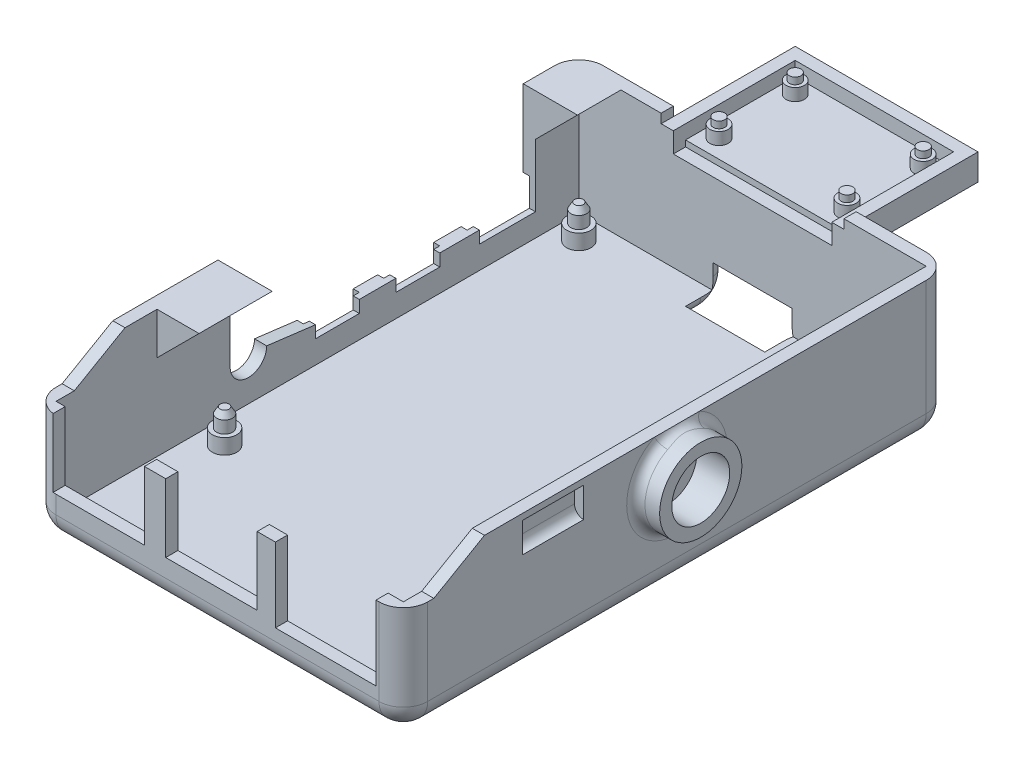
SolidWorks part; units mm, degrees
ref_plane "Płaszczyzna przednia" through (0, 0, 0) normal (0, 0, 1) x (1, 0, 0)
ref_plane "Płaszczyzna górna" through (0, 0, 0) normal (0, 1, 0) x (1, 0, 0)
ref_plane "Płaszczyzna prawa" through (0, 0, 0) normal (1, 0, 0) x (0, 0, -1)
sketch "Szkic1" plane through (0, 0, 0) normal (0, 1, 0) x (1, 0, 0)
  line L1 (-30.5, 44.9) -> (30.5, 44.9)
  line L2 (-30.5, 44.9) -> (-30.5, -44.9)
  line L3 (-30.5, -44.9) -> (30.5, -44.9)
  line L4 (30.5, 44.9) -> (30.5, -44.9)
  line L5 (-30.5, 44.9) -> (30.5, -44.9) construction
  line L6 (-30.5, -44.9) -> (30.5, 44.9) construction
  point P0 (0, 0)
  dimension "D1" = 61
  dimension "D2" = 89.8
extrude "Dodanie-wyciągnięcie1" add sketch "Szkic1" along normal blind 2
sketch "Szkic2" plane through (0, 2, 0) normal (0, 1, 0) x (1, 0, 0)
  line L0 (28.5, -42.9) -> (28.5, 42.9)
  line L1 (28.5, 42.9) -> (-28.5, 42.9)
  line L2 (-28.5, 42.9) -> (-28.5, -42.9)
  line L3 (-28.5, -42.9) -> (28.5, -42.9)
  line L4 (30.5, -44.9) -> (30.5, 44.9)
  line L5 (30.5, 44.9) -> (-30.5, 44.9)
  line L6 (-30.5, 44.9) -> (-30.5, -44.9)
  line L7 (-30.5, -44.9) -> (30.5, -44.9)
  line L8 (30.5, -44.9) -> (30.5, 44.9)
  line L9 (30.5, 44.9) -> (-30.5, 44.9)
  line L10 (-30.5, 44.9) -> (-30.5, -44.9)
  line L11 (-30.5, -44.9) -> (30.5, -44.9)
  dimension "D1" = 0
  dimension "D2" = 2
extrude "Dodanie-wyciągnięcie2" add sketch "Szkic2" along normal blind 16.15
sketch "Szkic3" plane through (0, 0, 44.9) normal (0, 0, 1) x (1, 0, 0)
  line L0 (-30.5, 18.15) -> (30.5, 18.15) construction
  line L1 (-27, 18.15) -> (-12, 18.15)
  line L2 (-27, 18.15) -> (-27, 6.95)
  line L3 (-27, 6.95) -> (-12, 6.95)
  line L4 (-12, 18.15) -> (-12, 6.95)
  line L5 (-30.5, 18.15) -> (-30.5, 0) construction
  line L6 (-8.5, 18.15) -> (6.5, 18.15)
  line L7 (-8.5, 18.15) -> (-8.5, 6.95)
  line L8 (-8.5, 6.95) -> (6.5, 6.95)
  line L9 (6.5, 18.15) -> (6.5, 6.95)
  line L10 (26, 18.15) -> (9.5, 18.15)
  line L11 (26, 18.15) -> (26, 5.95)
  line L12 (26, 5.95) -> (9.5, 5.95)
  line L13 (9.5, 18.15) -> (9.5, 5.95)
  dimension "D1" = 3.5
  dimension "D2" = 15
  dimension "D3" = 3.5
  dimension "D4" = 16.5
  dimension "D5" = 3
  dimension "D6" = 11.2
  dimension "D7" = 12.2
extrude "Wytnij-wyciągnięcie1" cut sketch "Szkic3" against normal up to surface (2 mm away) up to face at (0, 10.075, 42.9)
sketch "Szkic4" plane through (0, 0, -44.9) normal (0, 0, -1) x (-1, 0, 0)
  line L0 (-30.5, 0) -> (30.5, 0) construction
  line L1 (-6.5, 0) -> (6.5, 0)
  line L2 (-6.5, 0) -> (-6.5, 5.95)
  line L3 (-6.5, 5.95) -> (6.5, 5.95)
  line L4 (6.5, 0) -> (6.5, 5.95)
  line L5 (-6.5, 5.95) -> (-30.5, 5.95)
  line L7 (-30.5, 18.15) -> (-30.5, 0) construction
  line L8 (6.5, 5.95) -> (30.5, 5.95)
  line L9 (30.5, 18.15) -> (30.5, 0) construction
  dimension "D1" = 13
  dimension "D2" = 5.95
extrude "Wytnij-wyciągnięcie2" cut sketch "Szkic4" against normal blind 6.5 contours L2 L1 L4 L3
sketch "Szkic6" plane through (-30.5, 0, 0) normal (-1, 0, 0) x (0, 0, 1)
  line L0 (-35.77, 18.15) -> (14.33, 18.15)
  line L1 (-35.77, 18.15) -> (-35.77, 5.75)
  line L2 (-35.77, 5.75) -> (14.33, 5.75)
  line L3 (14.33, 18.15) -> (14.33, 5.75)
  line L4 (-26.57, 5.75) -> (-26.57, 7.75)
  line L5 (-26.57, 7.75) -> (-20.07, 7.75)
  line L6 (-20.07, 7.75) -> (-20.07, 5.75)
  line L7 (-12.87, 5.75) -> (-12.87, 7.75)
  line L8 (-12.87, 7.75) -> (-6.87, 7.75)
  line L9 (-6.87, 7.75) -> (-6.87, 5.75)
  line L10 (0.33, 5.75) -> (0.33, 7.75)
  line L11 (0.33, 7.75) -> (8.33, 8.75)
  line L12 (8.33, 8.75) -> (8.33, 5.75)
  line L13 (-6.87, 7.75) -> (0.33, 7.75) construction
  line L14 (-12.87, 7.75) -> (-20.07, 7.75) construction
  line L15 (-44.9, 18.15) -> (44.9, 18.15) construction
  line L16 (-44.9, 0) -> (44.9, 0) construction
  line L17 (-44.9, 18.15) -> (-44.9, 0) construction
  circle A0 centre (11.33, 8.75) radius 3
  line M7 (44.9, 18.15) -> (-44.9, 18.15)
  dimension "D2" = 6
  dimension "D1" = 50.1
  dimension "D3" = 9.2
  dimension "D4" = 7.2
  dimension "D5" = 6.5
  dimension "D6" = 6
  dimension "D7" = 2
  dimension "D8" = 5.75
  dimension "D9" = 9.13
extrude "Wytnij-wyciągnięcie4" cut sketch "Szkic6" against normal up to surface (2 mm away) contours A0 L3 L1 L2 L4 L5 L6 L7 L8 L9 L10 L11 M7 | A0 region at (-30.5, 12.5758, -12.3031) region at (-30.5, 8.75, 11.33) up to face at (-28.5, 10.075, 0)
sketch "Szkic7" plane through (0, 2, 0) normal (0, 1, 0) x (1, 0, 0)
  line L0 (24.57, 38.97) -> (24.57, -19.17) construction
  line L1 (24.57, -19.17) -> (-24.57, -19.17) construction
  line L2 (-24.57, -19.17) -> (-24.57, 38.97) construction
  line L3 (-24.57, 38.97) -> (24.57, 38.97) construction
  line L4 (0, 38.97) -> (0, -19.17) construction
  line L5 (-24.57, 9.9) -> (24.57, 9.9) construction
  line L7 (28.5, -42.9) -> (28.5, 42.9) construction
  line L8 (28.5, 42.9) -> (6.5, 42.9) construction
  line L9 (-28.5, 42.9) -> (-28.5, -42.9) construction
  line L10 (-28.5, -42.9) -> (28.5, -42.9) construction
  circle A0 centre (24.57, -19.17) radius 2
  circle A1 centre (-24.57, -19.17) radius 2
  circle A2 centre (24.57, 38.97) radius 2
  circle A3 centre (-24.57, 38.97) radius 2
  point P12 (0, 9.9)
  dimension "D1" = 4
  dimension "D2" = 3.93
  dimension "D5" = 23.73
  dimension "D3" = 3.93
  dimension "D4" = 3.93
extrude "Dodanie-wyciągnięcie3" add sketch "Szkic7" along normal blind 2.5
ref_plane "haczyki-przednia" through (0, 0, -9.9) normal (0, 0, 1) x (1, 0, 0)
ref_plane "haczyki-prawa" through (0, 0, 0) normal (-1, 0, 0) x (0, 0, 1)
sketch "Szkic8" plane through (0, 4.5, 0) normal (0, 1, 0) x (1, 0, 0)
  circle A0 centre (-24.57, 38.97) radius 1.3
  dimension "D1" = 2.6
extrude "Dodanie-wyciągnięcie4" add sketch "Szkic8" along normal blind 2
sketch "Szkic9" plane through (0, 6.5, 0) normal (0, 1, 0) x (1, 0, 0)
  circle A1 centre (-24.57, 38.97) radius 1.3
  circle A2 centre (-24.57, 38.97) radius 1.3
  dimension "D1" = 0
extrude "Dodanie-wyciągnięcie5" add sketch "Szkic9" along normal blind 1 draft 30
mirror "Lustro1" about plane through (0, 0, 0) normal (-1, 0, 0) of "Dodanie-wyciągnięcie5", "Dodanie-wyciągnięcie4"
mirror "Lustro2" about plane through (0, 0, -9.9) normal (0, 0, 1) of "Lustro1"
sketch "Szkic11" plane through (0, 18.15, 0) normal (0, 1, 0) x (1, 0, 0)
  line L0 (-28.5, 35.77) -> (-30.5, 35.77)
  line L1 (-30.5, 35.77) -> (-30.5, 44.9)
  line L2 (-30.5, 44.9) -> (-20.5, 44.9)
  line L3 (30.5, 44.9) -> (-30.5, 44.9) construction
  line L4 (-20.5, 44.9) -> (-20.5, 42.9)
  line L5 (28.5, 42.9) -> (-28.5, 42.9) construction
  line L6 (-20.5, 42.9) -> (-28.5, 42.9)
  line L7 (-28.5, 42.9) -> (-28.5, 35.77)
  line L8 (-30.5, -14.33) -> (-28.5, -14.33)
  line L9 (-28.5, -14.33) -> (-28.5, -44.9)
  line L10 (-30.5, -44.9) -> (-27, -44.9) construction
  line L11 (-28.5, -44.9) -> (-30.5, -44.9)
  line L12 (-30.5, -44.9) -> (-30.5, -14.33)
  dimension "D1" = 10
extrude "Dodanie-wyciągnięcie6" add sketch "Szkic11" along normal blind 4.8
sketch "Szkic12" plane through (-30.5, 0, 0) normal (-1, 0, 0) x (0, 0, 1)
  line L5 (44.9, 18.15) -> (39.9, 18.15)
  line L6 (44.9, 22.95) -> (44.9, 0) construction
  line L7 (39.9, 18.15) -> (31.5862, 22.95)
  line L8 (14.33, 22.95) -> (44.9, 22.95) construction
  line L9 (31.5862, 22.95) -> (44.9, 22.95)
  line L10 (44.9, 22.95) -> (44.9, 18.15)
  line L11 (44.9, 18.15) -> (42.9, 18.15) construction
  dimension "D1" = 30
  dimension "D2" = 5
extrude "Wytnij-wyciągnięcie5" cut sketch "Szkic12" against normal up to surface (2 mm away) up to face at (-28.5, 10.469, -3.6595)
sketch "Szkic13" plane through (0, 0, 14.33) normal (0, 0, -1) x (-1, 0, 0)
  line L0 (28.5, 22.95) -> (21.6, 22.95)
  line L1 (21.6, 22.95) -> (28.5, 16.05)
  line L2 (28.5, 22.95) -> (28.5, 8.75) construction
  line L3 (28.5, 16.05) -> (28.5, 22.95)
  dimension "D1" = 45
  dimension "D2" = 6.9
extrude "Dodanie-wyciągnięcie7" add sketch "Szkic13" against normal blind 12
sketch "Szkic14" plane through (0, 0, -35.77) normal (0, 0, 1) x (1, 0, 0)
  line L0 (-21.6, 22.95) -> (-28.5, 22.95)
  line L1 (-28.5, 22.95) -> (-28.5, 16.05)
  line L5 (-21.6, 22.95) -> (-30.5, 22.95)
  line L6 (-28.5, 16.05) -> (-21.6, 22.95)
  line L7 (-28.5, 8.75) -> (-28.5, 16.05)
  line L8 (-30.5, 8.75) -> (-28.5, 8.75)
  line L9 (-30.5, 22.95) -> (-30.5, 8.75)
  line L11 (-28.5, 16.05) -> (-21.6, 22.95)
  dimension "D1" = 0
extrude "Dodanie-wyciągnięcie8" add sketch "Szkic14" against normal up to surface (7.13 mm away) up to face at (-4.1, 10.21, -42.9)
sketch "Szkic15" plane through (-30.5, 0, 0) normal (-1, 0, 0) x (0, 0, 1)
  line L0 (14.33, 22.95) -> (31.5862, 22.95) construction
  line L1 (-39.9, 21.95) -> (-36.77, 21.95)
  line L2 (-39.9, 21.95) -> (-39.9, 17.05)
  line L3 (-39.9, 17.05) -> (-36.77, 17.05)
  line L4 (-36.77, 21.95) -> (-36.77, 17.05)
  line L5 (15.33, 21.95) -> (25.33, 21.95)
  line L6 (15.33, 21.95) -> (15.33, 17.05)
  line L7 (15.33, 17.05) -> (25.33, 17.05)
  line L8 (25.33, 21.95) -> (25.33, 17.05)
  line L9 (-44.9, 22.95) -> (-44.9, 0) construction
  line L10 (14.33, 22.95) -> (14.33, 8.75) construction
  line L11 (26.33, 16.05) -> (14.33, 16.05) construction
  line L12 (26.33, 16.05) -> (26.33, 22.95) construction
  line L15 (-35.77, 22.95) -> (-35.77, 5.75) construction
  dimension "D1" = 1
  dimension "D2" = 1
  dimension "D3" = 1
  dimension "D4" = 1
  dimension "D5" = 1
  dimension "D6" = 5
extrude "Wytnij-wyciągnięcie6" cut sketch "Szkic15" against normal up to surface (7.9 mm away) up to face at (-25.05, 19.5, -39.335)
sketch "Szkic16" plane through (0, 0, -39.9) normal (0, 0, 1) x (1, 0, 0)
  line L0 (-27.5, 17.05) -> (-22.6, 21.95)
  line L1 (-22.6, 21.95) -> (-24.0142, 21.95)
  line L2 (-22.6, 21.95) -> (-30.5, 21.95) construction
  line L3 (-24.0142, 21.95) -> (-28.9142, 17.05)
  line L4 (-27.5, 17.05) -> (-30.5, 17.05) construction
  line L5 (-28.9142, 17.05) -> (-27.5, 17.05)
  dimension "D1" = 1
extrude "Dodanie-wyciągnięcie9" add sketch "Szkic16" along normal up to surface (3.13 mm away) up to face at (-27.775, 19.5, -36.77)
sketch "Szkic17" plane through (0, 0, 25.33) normal (0, 0, -1) x (-1, 0, 0)
  line L0 (27.5, 17.05) -> (28.9142, 17.05)
  line L1 (27.5, 17.05) -> (30.5, 17.05) construction
  line L2 (28.9142, 17.05) -> (24.0142, 21.95)
  line L3 (22.6, 21.95) -> (30.5, 21.95) construction
  line L4 (24.0142, 21.95) -> (22.6, 21.95)
  line L5 (22.6, 21.95) -> (27.5, 17.05)
  dimension "D1" = 1
extrude "Dodanie-wyciągnięcie10" add sketch "Szkic17" along normal up to surface (10 mm away) up to face at (-27.775, 19.5, 15.33)
fillet "Zaokrąglenie1" radius 4 9 edges at (-18.5, 0, -44.9) (18.5, 0, -44.9) (30.5, 0, 0) (0, 0, 44.9) (-30.5, 0, 0) (-30.5, 9.075, 44.9) (30.5, 9.075, 44.9) (30.5, 9.075, -44.9) (-30.5, 11.475, -44.9)
fillet "Zaokrąglenie2" radius 2 8 edges at (-6.5, 4.975, -44.9) (-6.5, 1.1716, -43.7284) (6.5, 4.975, -44.9) (6.5, 1.1716, -43.7284) (0, 5.95, -44.9) (-6.5, 0, -39.65) (6.5, 0, -39.65) (0, 0, -38.4)
sketch "Szkic19" plane through (0, 18.15, 0) normal (0, 1, 0) x (1, 0, 0)
  line L0 (30.5, -31.5862) -> (28.5, -31.5862)
  line L1 (-28.5, -31.5862) -> (-30.5, -31.5862) construction
  line L8 (26, -44.9) -> (26.5, -44.9)
  line L9 (30.5, -40.9) -> (30.5, 40.9)
  line L10 (26.5, 44.9) -> (-20.5, 44.9)
  line L11 (-20.5, 44.9) -> (-20.5, 42.9)
  line L12 (-20.5, 42.9) -> (28.5, 42.9)
  line L13 (28.5, 42.9) -> (28.5, -42.9)
  line L14 (28.5, -42.9) -> (26, -42.9)
  line L15 (26, -42.9) -> (26, -44.9)
  line L16 (26, -44.9) -> (26.5, -44.9)
  line L17 (30.5, -40.9) -> (30.5, 40.9)
  line L18 (26.5, 44.9) -> (-20.5, 44.9)
  line L19 (-20.5, 44.9) -> (-20.5, 42.9)
  line L20 (-20.5, 42.9) -> (28.5, 42.9)
  line L21 (28.5, 42.9) -> (28.5, -42.9)
  line L22 (28.5, -42.9) -> (26, -42.9)
  line L23 (26, -42.9) -> (26, -44.9)
  arc A2 (26.5, -44.9) -> (30.5, -40.9) centre (26.5, -40.9) ccw
  arc A3 (30.5, 40.9) -> (26.5, 44.9) centre (26.5, 40.9) ccw
  arc A4 (26.5, -44.9) -> (30.5, -40.9) centre (26.5, -40.9) ccw
  arc A5 (30.5, 40.9) -> (26.5, 44.9) centre (26.5, 40.9) ccw
  point P12 (-29.5, -31.5862)
  line M14 (30.5, -40.9) -> (30.5, 40.9)
  arc M15 (30.5, 40.9) -> (26.5, 44.9) centre (26.5, 40.9) ccw
  line M16 (26.5, 44.9) -> (-20.5, 44.9)
  line M17 (-20.5, 44.9) -> (-20.5, 42.9)
  line M18 (-20.5, 42.9) -> (28.5, 42.9)
  line M19 (28.5, 42.9) -> (28.5, -42.9)
  dimension "D1" = 0
extrude "Dodanie-wyciągnięcie11" add sketch "Szkic19" along normal up to surface (4.8 mm away) contours L0 M14 M15 M16 M17 M18 M19 region at (29.5, 18.15, 30.6669) up to face at (-26.8667, 22.95, 24.0821)
sketch "Szkic20" plane through (30.5, 0, 0) normal (1, 0, 0) x (0, 0, -1)
  line L0 (-39.9, 18.15) -> (-31.5862, 18.15)
  line L1 (-31.5862, 18.15) -> (-31.5862, 22.95)
  line L22 (42.9, 16.05) -> (35.77, 16.05)
  line L23 (35.77, 16.05) -> (35.77, 5.75)
  line L24 (35.77, 5.75) -> (26.57, 5.75)
  line L25 (26.57, 5.75) -> (26.57, 7.75)
  line L26 (26.57, 7.75) -> (20.07, 7.75)
  line L27 (20.07, 7.75) -> (20.07, 5.75)
  line L28 (20.07, 5.75) -> (12.87, 5.75)
  line L29 (12.87, 5.75) -> (12.87, 7.75)
  line L30 (12.87, 7.75) -> (6.87, 7.75)
  line L31 (6.87, 7.75) -> (6.87, 5.75)
  line L32 (6.87, 5.75) -> (-0.33, 5.75)
  line L33 (-0.33, 5.75) -> (-0.33, 7.75)
  line L34 (-0.33, 7.75) -> (-8.33, 8.75)
  line L35 (-14.33, 8.75) -> (-14.33, 16.05)
  line L36 (-14.33, 16.05) -> (-26.33, 16.05)
  line L37 (-26.33, 16.05) -> (-26.33, 22.95)
  line L38 (-26.33, 22.95) -> (-31.5862, 22.95)
  line L39 (-31.5862, 22.95) -> (-39.9, 18.15)
  line L40 (-39.9, 18.15) -> (-42.9, 18.15)
  line L41 (-42.9, 18.15) -> (-42.9, 2)
  line L42 (-42.9, 2) -> (42.9, 2)
  line L43 (42.9, 2) -> (42.9, 16.05)
  line L44 (42.9, 16.05) -> (35.77, 16.05)
  line L45 (35.77, 16.05) -> (35.77, 5.75)
  line L46 (35.77, 5.75) -> (26.57, 5.75)
  line L47 (26.57, 5.75) -> (26.57, 7.75)
  line L48 (26.57, 7.75) -> (20.07, 7.75)
  line L49 (20.07, 7.75) -> (20.07, 5.75)
  line L50 (20.07, 5.75) -> (12.87, 5.75)
  line L51 (12.87, 5.75) -> (12.87, 7.75)
  line L52 (12.87, 7.75) -> (6.87, 7.75)
  line L53 (6.87, 7.75) -> (6.87, 5.75)
  line L54 (6.87, 5.75) -> (-0.33, 5.75)
  line L55 (-0.33, 5.75) -> (-0.33, 7.75)
  line L56 (-0.33, 7.75) -> (-8.33, 8.75)
  line L57 (-14.33, 8.75) -> (-14.33, 16.05)
  line L58 (-14.33, 16.05) -> (-26.33, 16.05)
  line L59 (-26.33, 16.05) -> (-26.33, 22.95)
  line L60 (-26.33, 22.95) -> (-31.5862, 22.95)
  line L61 (-31.5862, 22.95) -> (-39.9, 18.15)
  line L62 (-39.9, 18.15) -> (-42.9, 18.15)
  line L63 (-42.9, 18.15) -> (-42.9, 2)
  line L64 (-42.9, 2) -> (42.9, 2)
  line L65 (42.9, 2) -> (42.9, 16.05)
  arc A1 (-14.33, 8.75) -> (-8.33, 8.75) centre (-11.33, 8.75) ccw
  arc A2 (-14.33, 8.75) -> (-8.33, 8.75) centre (-11.33, 8.75) ccw
  line M24 (-31.5862, 18.15) -> (-40.9, 18.15)
  line M29 (-31.5862, 22.95) -> (-31.5862, 18.15)
  dimension "D1" = 0
extrude "Dodanie-wyciągnięcie12" add sketch "Szkic20" against normal up to surface (2 mm away) contours L61 M29 M24 region at (30.5, 19.75, 34.3574) up to face at (28.5, 14.3667, 10.5287)
sketch "Szkic18" plane through (0, 0, -44.9) normal (0, 0, -1) x (-1, 0, 0)
  line L12 (-15, 22.95) -> (-15, 21.45)
  line L17 (-26.5, 22.95) -> (26.5, 22.95) construction
  line L18 (-15, 21.45) -> (-13, 21.45)
  line L19 (-13, 21.45) -> (-13, 18.15)
  line L20 (-13, 18.15) -> (13, 18.15)
  line L21 (13, 18.15) -> (13, 21.45)
  line L22 (13, 21.45) -> (15, 21.45)
  line L23 (15, 21.45) -> (15, 22.95)
  line L24 (15, 22.95) -> (-15, 22.95)
  line L25 (-13, 18.15) -> (-30.5, 18.15) construction
  line L26 (-30.5, 4) -> (-30.5, 22.95) construction
  line L27 (13, 18.15) -> (30.5, 18.15) construction
  line L28 (30.5, 22.95) -> (30.5, 4) construction
  dimension "D1" = 1.5
  dimension "D2" = 2
  dimension "D3" = 3.3
  dimension "D4" = 26
extrude "Wytnij-wyciągnięcie7" cut sketch "Szkic18" against normal up to surface (2 mm away) up to face at (-1.9643, 8.2748, -42.9)
sketch "Szkic21" plane through (0, 0, -44.9) normal (0, 0, -1) x (-1, 0, 0)
  line L0 (-15, 21.45) -> (-13, 21.45)
  line L1 (-13, 21.45) -> (-13, 19.15)
  line L2 (-13, 21.45) -> (-13, 18.15) construction
  line L3 (-13, 19.15) -> (13, 19.15)
  line L4 (13, 18.15) -> (13, 21.45) construction
  line L5 (13, 19.15) -> (13, 21.45)
  line L6 (13, 21.45) -> (15, 21.45)
  line L7 (15, 21.45) -> (15, 17.15)
  line L8 (15, 17.15) -> (-15, 17.15)
  line L9 (-15, 17.15) -> (-15, 21.45)
  line L10 (0, 17.15) -> (0, 18.15) construction
  line L11 (-13, 18.15) -> (13, 18.15) construction
  line L12 (0, 18.15) -> (0, 19.15) construction
  dimension "D1" = 2
extrude "Dodanie-wyciągnięcie13" add sketch "Szkic21" along normal blind 20
sketch "Szkic22" plane through (0, 19.15, 0) normal (0, 1, 0) x (1, 0, 0)
  line L0 (13, 64.9) -> (-13, 64.9)
  line L1 (-13, 64.9) -> (-13, 62.9)
  line L2 (-13, 64.9) -> (-13, 44.9) construction
  line L3 (-13, 62.9) -> (13, 62.9)
  line L4 (13, 42.9) -> (13, 64.9) construction
  line L5 (13, 62.9) -> (13, 64.9)
  line L6 (13, 64.9) -> (15, 64.9) construction
extrude "Dodanie-wyciągnięcie14" add sketch "Szkic22" along normal up to surface (2.3 mm away) up to face at (14.2, 21.45, -52.1)
sketch "Szkic23" plane through (0, 19.15, 0) normal (0, 1, 0) x (1, 0, 0)
  line L0 (-10.5, 60.4) -> (10.5, 60.4) construction
  line L1 (10.5, 60.4) -> (10.5, 47.9) construction
  line L2 (10.5, 47.9) -> (-10.5, 47.9) construction
  line L3 (-10.5, 47.9) -> (-10.5, 60.4) construction
  line L4 (0, 60.4) -> (0, 47.9) construction
  line L5 (10.5, 54.15) -> (-10.5, 54.15) construction
  line L6 (10.5, 54.15) -> (13, 54.15) construction
  line L8 (-10.5, 54.15) -> (-13, 54.15) construction
  line L10 (13, 62.9) -> (13, 44.9) construction
  line L11 (-13, 62.9) -> (13, 62.9) construction
  line L12 (-13, 62.9) -> (-13, 44.9) construction
  circle A0 centre (10.5, 47.9) radius 1.5
  circle A1 centre (-10.5, 47.9) radius 1.5
  circle A2 centre (-10.5, 60.4) radius 1.5
  circle A3 centre (10.5, 60.4) radius 1.5
  point P12 (0, 54.15)
  dimension "D1" = 3
  dimension "D2" = 2.5
  dimension "D3" = 2.5
  dimension "D4" = 12.5
extrude "Dodanie-wyciągnięcie15" add sketch "Szkic23" along normal blind 2
ref_plane "cam przednia" through (0, 0, -54.15) normal (0, 0, -1) x (-1, 0, 0)
ref_plane "cam prawa" through (0, 0, 0) normal (-1, 0, 0) x (0, 0, 1)
sketch "Szkic24" plane through (0, 21.15, 0) normal (0, 1, 0) x (1, 0, 0)
  circle A0 centre (-10.5, 60.4) radius 0.95
  dimension "D1" = 1.9
extrude "Dodanie-wyciągnięcie16" add sketch "Szkic24" along normal blind 1.1
mirror "Lustro3" about plane through (0, 0, 0) normal (-1, 0, 0) of "Dodanie-wyciągnięcie16"
mirror "Lustro4" about plane through (0, 0, -54.15) normal (0, 0, -1) of "Lustro3"
sketch "Szkic25" plane through (-30.5, 0, 0) normal (-1, 0, 0) x (0, 0, 1)
  line L0 (-35.77, 5.75) -> (-35.77, 10.35)
  line L1 (-35.77, 22.95) -> (-35.77, 5.75) construction
  line L2 (-35.77, 10.35) -> (-36.77, 10.35)
  line L3 (-36.77, 10.35) -> (-36.77, 4.75)
  line L4 (-36.77, 4.75) -> (-25.57, 4.75)
  line L5 (-25.57, 4.75) -> (-25.57, 7.75)
  line L6 (-26.57, 7.75) -> (-20.07, 7.75) construction
  line L7 (-25.57, 7.75) -> (-26.57, 7.75)
  line L8 (-26.57, 7.75) -> (-26.57, 5.75)
  line L9 (-35.77, 5.75) -> (-26.57, 5.75) construction
  line L10 (-26.57, 5.75) -> (-35.77, 5.75)
  line L11 (-20.07, 5.75) -> (-20.07, 7.75)
  line L12 (-20.07, 7.75) -> (-21.07, 7.75)
  line L13 (-21.07, 7.75) -> (-21.07, 4.75)
  line L14 (-21.07, 4.75) -> (-11.87, 4.75)
  line L15 (-11.87, 4.75) -> (-11.87, 7.75)
  line L16 (-12.87, 7.75) -> (-6.87, 7.75) construction
  line L17 (-11.87, 7.75) -> (-12.87, 7.75)
  line L18 (-12.87, 7.75) -> (-12.87, 5.75)
  line L19 (-12.87, 5.75) -> (-20.07, 5.75)
  line L20 (-6.87, 5.75) -> (-6.87, 7.75)
  line L21 (-6.87, 7.75) -> (-7.87, 7.75)
  line L22 (-7.87, 7.75) -> (-7.87, 4.75)
  line L23 (-7.87, 4.75) -> (1.33, 4.75)
  line L24 (1.33, 4.75) -> (1.33, 7.875)
  line L25 (0.33, 7.75) -> (8.33, 8.75) construction
  line L26 (1.33, 7.875) -> (0.33, 7.75)
  line L27 (0.33, 7.75) -> (0.33, 5.75)
  line L28 (0.33, 5.75) -> (-6.87, 5.75)
  line L29 (0.33, 7.75) -> (1.33, 7.75) construction
  line L30 (-26.57, 5.75) -> (-26.57, 7.75) construction
  dimension "D1" = 1
  dimension "D2" = 1
  dimension "D3" = 1
  dimension "D4" = 4.6
extrude "Wytnij-wyciągnięcie8" cut sketch "Szkic25" against normal blind 1
sketch "Szkic26" plane through (30.5, 0, 0) normal (1, 0, 0) x (0, 0, -1)
  line L0 (-25.33, 17.05) -> (-25.33, 21.95) construction
  line L1 (-25.33, 21.95) -> (-15.33, 21.95)
  line L2 (-25.33, 21.95) -> (-25.33, 17.05)
  line L3 (-25.33, 17.05) -> (-15.33, 17.05)
  line L4 (-15.33, 21.95) -> (-15.33, 17.05)
  line L5 (-15.33, 21.95) -> (-15.33, 17.05) construction
  line L6 (-25.33, 21.95) -> (-15.33, 21.95) construction
  line L7 (-15.33, 17.05) -> (-25.33, 17.05) construction
extrude "Wytnij-wyciągnięcie9" cut sketch "Szkic26" against normal blind 1.5
fillet "Zaokrąglenie3" radius 1.5 1 edges at (29, 17.05, 20.33)
sketch "Szkic28" plane through (30.5, 0, 0) normal (1, 0, 0) x (0, 0, -1)
  line L0 (-4.75, 15.575) -> (-40.9, 15.575) construction
  line L1 (-40.9, 18.15) -> (-40.9, 4) construction
  line L2 (4.75, 15.575) -> (40.9, 15.575) construction
  line L3 (40.9, 4) -> (40.9, 22.95) construction
  line L4 (0, 20.325) -> (0, 22.95) construction
  line L6 (40.9, 22.95) -> (-31.5862, 22.95) construction
  line L8 (0, 10.825) -> (0, 8.2) construction
  line L9 (0, 8.2) -> (0, 0) construction
  line L11 (40.9, 0) -> (-40.9, 0) construction
  circle A0 centre (0, 15.575) radius 4.75
  point P17 (0, 2.247)
  point P18 (0, 8.235)
  point P20 (0, 0)
  point P23 (0, 0)
  dimension "D1" = 9.5
  dimension "D2" = 8.2
extrude "Wytnij-wyciągnięcie10" cut sketch "Szkic28" against normal blind 1.5
sketch "Szkic29" plane through (30.5, 0, 0) normal (1, 0, 0) x (0, 0, -1)
  circle A0 centre (0, 15.575) radius 4.75 construction
  circle A1 centre (0, 15.575) radius 4.75
  circle A2 centre (0, 15.575) radius 6.75
  dimension "D1" = 2
extrude "Dodanie-wyciągnięcie17" add sketch "Szkic29" along normal blind 3.9
fillet "Zaokrąglenie4" radius 1.5 1 edges at (30.5, 15.575, 6.75)
